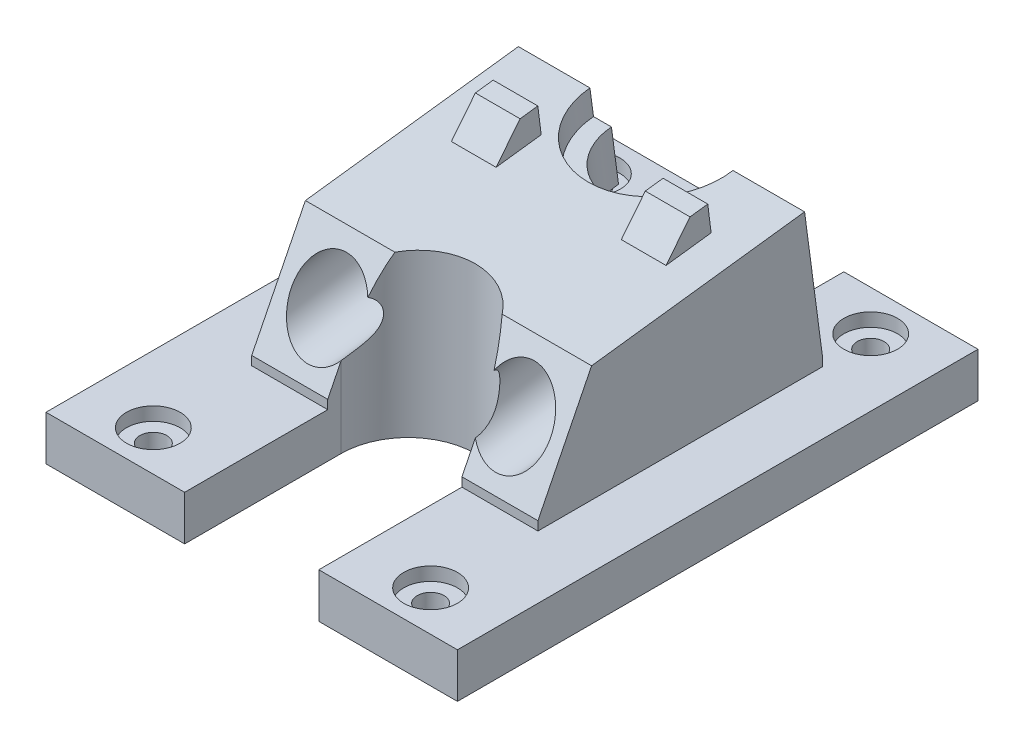
SolidWorks part; units mm, degrees
note: The reader was unsure of these and kept them because the rebuilt part matched: shared geometry of "Sketch1<3>", "Sketch2<3>", "Sketch3<3>", "Sketch3<4>", "Sketch1<4>", "Sketch4<3>", "Sketch4<4>".
ref_plane "Front Plane" through (0, 0, 0) normal (0, 0, 1) x (1, 0, 0)
ref_plane "Top Plane" through (0, 0, 0) normal (0, 1, 0) x (1, 0, 0)
ref_plane "Right Plane" through (0, 0, 0) normal (1, 0, 0) x (0, 0, -1)
sketch "Sketch1" plane through (0, 0, 0) normal (0, 1, 0) x (1, 0, 0)
  line L0 (-8, 29.1) -> (-8, 19.1)
  line L1 (-23, 29.1) -> (-8, 29.1)
  line L2 (-23, 29.1) -> (-23, -29.1)
  line L3 (-23, -29.1) -> (-7.5, -29.1)
  line L4 (23, 29.1) -> (23, -29.1)
  line L5 (-23, 29.1) -> (23, -29.1) construction
  line L6 (-23, -29.1) -> (23, 29.1) construction
  line L7 (0, 29.1) -> (0, -29.1) construction
  line L8 (8, 29.1) -> (8, 19.1)
  line L9 (8, 29.1) -> (23, 29.1)
  line L10 (-23, 0) -> (23, 0) construction
  line L11 (-7.5, -11.6) -> (-7.5, -29.1)
  line L12 (7.5, -11.6) -> (7.5, -29.1)
  line L13 (7.5, -29.1) -> (23, -29.1)
  line L14 (7.5, -29.1) -> (-7.5, -29.1)
  arc A0 (-8, 19.1) -> (8, 19.1) centre (0, 19.1) ccw
  circle A1 centre (-15.5, 24.6) radius 3
  circle A2 centre (-15.5, 24.6) radius 1.5
  circle A5 centre (-15.5, -24.6) radius 1.5
  circle A6 centre (-15.5, -24.6) radius 3
  circle A7 centre (15.5, 24.6) radius 1.5
  circle A8 centre (15.5, 24.6) radius 3
  circle A9 centre (15.5, -24.6) radius 1.5
  circle A10 centre (15.5, -24.6) radius 3
  arc A11 (7.5, -11.6) -> (-7.5, -11.6) centre (0, -11.6) ccw
  point P0 (0, 0)
  point P19 (-15.5, 29.1)
  dimension "D5" = 16
  dimension "D6" = 6
  dimension "D7" = 3
  dimension "D9" = 15
  dimension "D1" = 46
  dimension "D2" = 58.2
  dimension "D3" = 16
  dimension "D4" = 10
  dimension "D8" = 4.5
  dimension "D10" = 17.5
extrude "Boss-Extrude1" add sketch "Sketch1" along normal blind 5 contours A11 L12 L13 L4 L9 L8 A0 L0 L1 L2 L3 L11 A10 A1 A6 A8 | A6 A5 | A10 A9 | A8 A7 | A1 A2
extrude "Cut-Extrude1" cut sketch "Sketch1<3>" against normal blind 1.5 from surface at 5 contours A6 A5 | A10 A9 | A8 A7 | A1 A2 starting at face at (0, 5, -1.2083)
sketch "Sketch1<3>" plane through (0, 0, 0) normal (0, 1, 0) x (1, 0, 0) same geometry as "Sketch1"
sketch "Sketch2" plane through (0, 0, 0) normal (1, 0, 0) x (0, 0, -1)
  line L0 (-13.1, 6) -> (-13.1, 5)
  line L1 (29.1, 5) -> (-29.1, 5) construction
  line L2 (-29.1, 5) -> (-29.1, 0) construction
  line L3 (-13.1, 6) -> (-7.1, 18)
  line L4 (18.7118, 5) -> (18.7118, 6)
  line L5 (18.7118, 6) -> (16.7118, 21)
  line L6 (-7.1, 18) -> (16.7118, 21)
  line L7 (-13.1, 5) -> (18.7118, 5)
  line L8 (7.9034, 22.914) -> (9.8877, 23.164)
  line L9 (7.9034, 22.914) -> (5.222, 19.5524)
  line L10 (9.8877, 23.164) -> (10.2627, 20.1875)
  point P12 (2.5503, 19.2158)
  point P15 (6.6028, 19.7264)
  point P16 (0.3538, 18.9391)
  point P17 (10.6529, 24.5586)
  dimension "D1" = 1
  dimension "D2" = 16
  dimension "D3" = 12
  dimension "D4" = 6
  dimension "D5" = 15
  dimension "D6" = 2
  dimension "D7" = 24
  dimension "D8" = 2
  dimension "D9" = 4.3
  dimension "D10" = 3
  dimension "D11" = 6.5
extrude "Boss-Extrude2" add sketch "Sketch2" along normal mid plane 32 contours L0 L7 L4 L5 L6 L3
extrude "Boss-Extrude3" add sketch "Sketch2<3>" along normal blind 5 from offset 7 contours L10 L8 L9 L6
sketch "Sketch2<3>" plane through (0, 0, 0) normal (1, 0, 0) x (0, 0, -1) same geometry as "Sketch2"
mirror "Mirror1" about plane through (0, 0, 0) normal (1, 0, 0) of "Boss-Extrude3"
sketch "Sketch3" plane through (0, 2.5561, -19.1709) normal (0, 0.1322, -0.9912) x (-1, 0, 0)
  line L0 (-16, 3.4744) -> (-16, 18.6071) construction
  line L1 (-16, 18.6071) -> (16, 18.6071) construction
  line L2 (0, 0) -> (0, 21.8944) construction
  circle A0 centre (-10.5, 13.1071) radius 1.75
  circle A1 centre (-10.5, 13.1071) radius 2.5
  circle A2 centre (-10.5, 13.1071) radius 4
  circle A4 centre (10.5, 13.1071) radius 4
  circle A5 centre (10.5, 13.1071) radius 2.5
  circle A6 centre (10.5, 13.1071) radius 1.75
  dimension "D1" = 1.75
  dimension "D2" = 2.5
  dimension "D3" = 4
  dimension "D4" = 5.5
  dimension "D5" = 5.5
extrude "Cut-Extrude2" cut sketch "Sketch3" against normal through all contours A6 | A0
extrude "Cut-Extrude3" cut sketch "Sketch3<3>" against normal through all from offset 14 contours A5 A6 | A1 A0 offset against normal yes
sketch "Sketch3<3>" plane through (0, 2.5561, -19.1709) normal (0, 0.1322, -0.9912) x (-1, 0, 0) same geometry as "Sketch3"
extrude "Cut-Extrude4" cut sketch "Sketch3<4>" against normal through all from offset 19 contours A4 A5 | A2 A1 offset against normal yes
sketch "Sketch3<4>" plane through (0, 2.5561, -19.1709) normal (0, 0.1322, -0.9912) x (-1, 0, 0) same geometry as "Sketch3"
extrude "Cut-Extrude5" cut sketch "Sketch1<4>" along normal through all contours L12 A11 L11 L14
sketch "Sketch1<4>" plane through (0, 0, 0) normal (0, 1, 0) x (1, 0, 0) same geometry as "Sketch1"
sketch "Sketch4" plane through (0, 18.7463, 1.1763) normal (0, -0.9922, -0.125) x (1, 0, 0)
  circle A1 centre (0, -17.7739) radius 8
  circle A5 centre (0, -17.7739) radius 6
  ellipse E0 centre (0, -17.7739) end of major axis (-8, -17.7739) minor radius 7.9373 (8, -17.7739) -> (-8, -17.7739) ccw construction
  ellipse E2 centre (0, -17.7739) end of major axis (-8, -17.7739) minor radius 7.9373 (8, -17.7739) -> (-8, -17.7739) ccw construction
  line M31 (16, -18.0294) -> (-16, -18.0294)
  dimension "D1" = 12
  dimension "D2" = 16
extrude "Cut-Extrude6" cut sketch "Sketch4" along normal blind 3 contours A5 M31 | A5 M31 | A5 A1 M31 | A5 A1 M31
extrude "Cut-Extrude7" cut sketch "Sketch4<3>" along normal blind 6 from surface at 3 contours A5 M31 | A5 M31 starting at face at (0, 17.5089, -13.0021)
sketch "Sketch4<3>" plane through (0, 18.7463, 1.1763) normal (0, -0.9922, -0.125) x (1, 0, 0) same geometry as "Sketch4"
extrude "Cut-Extrude8" cut sketch "Sketch4<4>" along normal through all from surface contours A5 M31 | A5 M31 | A5 A1 M31 | A5 A1 M31
sketch "Sketch4<4>" plane through (0, 18.7463, 1.1763) normal (0, -0.9922, -0.125) x (1, 0, 0) same geometry as "Sketch4"
